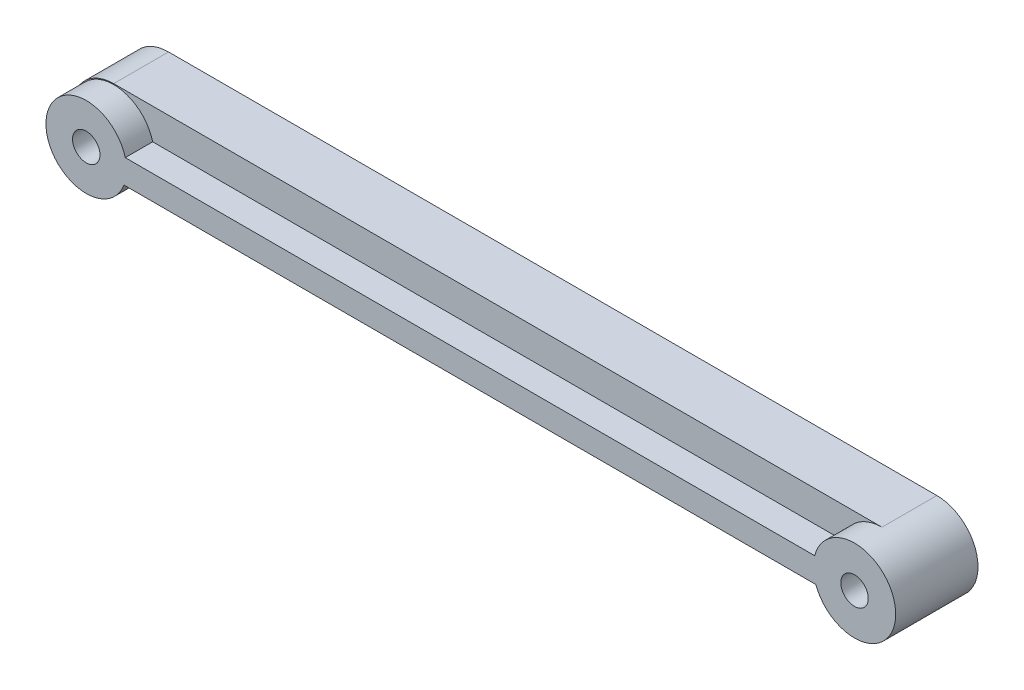
SolidWorks part; units mm, degrees
ref_plane "前视基准面" through (0, 0, 0) normal (0, 0, 1) x (1, 0, 0)
ref_plane "上视基准面" through (0, 0, 0) normal (0, 1, 0) x (1, 0, 0)
ref_plane "右视基准面" through (0, 0, 0) normal (1, 0, 0) x (0, 0, -1)
other "Configuration Table"
sketch "草图1" plane through (0, 0, 0) normal (0, 0, 1) x (1, 0, 0)
  line L0 (-1000, 0) -> (0, 0) construction
  line L2 (0, 1.5) -> (28, 1.5)
  line L3 (0, -1.5) -> (28, -1.5)
  line L4 (29.5, 0) -> (49000, 0) construction
  arc A0 (0, 1.5) -> (0, -1.5) centre (0, 0) ccw
  arc A1 (28, -1.5) -> (28, 1.5) centre (28, 0) ccw
  circle A2 centre (0, 0) radius 0.5
  circle A3 centre (28, 0) radius 0.5
  dimension "D1" = 3
  dimension "D3" = 1.5
  dimension "D4" = 1
  dimension "D5" = 1
  dimension "D2" = 28
extrude "凸台-拉伸1" add sketch "草图1" along normal blind 2
sketch "草图2" plane through (0, 0, 2) normal (0, 0, 1) x (1, 0, 0)
  line L0 (1.4203, 0.3745) -> (26.5475, 0.3745)
  line L1 (26.5907, -0.5138) -> (1.3761, -0.5138)
  arc A0 (1.4203, 0.3745) -> (1.3761, -0.5138) centre (0, 0) ccw
  arc A2 (26.5907, -0.5138) -> (26.5475, 0.3745) centre (28, 0) ccw
  circle A4 centre (0, 0) radius 0.5
  circle A5 centre (28, 0) radius 0.5
extrude "凸台-拉伸3" add sketch "草图2" along normal blind 1
